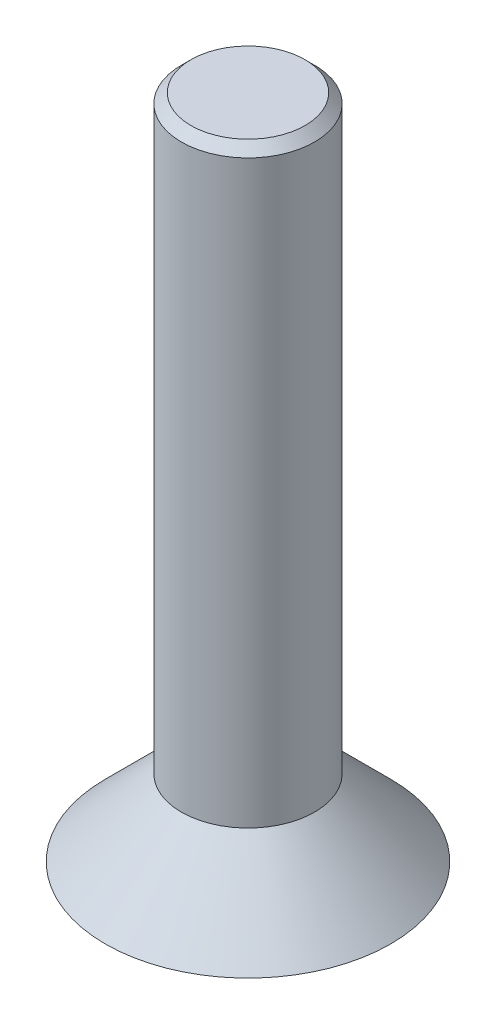
SolidWorks part; units mm, degrees
material "铸造合金钢"
ref_plane "前视基准面" through (0, 0, 0) normal (0, 0, 1) x (1, 0, 0)
ref_plane "上视基准面" through (0, 0, 0) normal (0, 1, 0) x (1, 0, 0)
ref_plane "右视基准面" through (0, 0, 0) normal (1, 0, 0) x (0, 0, -1)
sketch "草图1" plane through (0, 0, 0) normal (0, 1, 0) x (1, 0, 0)
  line L1 (0, -1.1547) -> (1, -0.5774)
  line L2 (1, -0.5774) -> (1, 0.5774)
  line L3 (1, 0.5774) -> (0, 1.1547)
  line L4 (0, 1.1547) -> (-1, 0.5774)
  line L5 (-1, 0.5774) -> (-1, -0.5774)
  line L6 (-1, -0.5774) -> (0, -1.1547)
  circle A0 centre (0, 0) radius 3
  circle A1 centre (0, 0) radius 1 construction
  dimension "D1" = 6
  dimension "D2" = 2
extrude "凸台-拉伸1" add sketch "草图1" along normal blind 1.6
chamfer "倒角1" distance 1.6 angle 45 1 edges at (0, 1.6, 3)
sketch "草图2" plane through (0, 1.6, 0) normal (0, 1, 0) x (1, 0, 0)
  circle A0 centre (0, 0) radius 1.4
  dimension "D1" = 2.8
extrude "凸台-拉伸2" add sketch "草图2" along normal blind 12.4
chamfer "倒角2" distance 0.2 angle 45 1 edges at (0, 14, 1.4)
